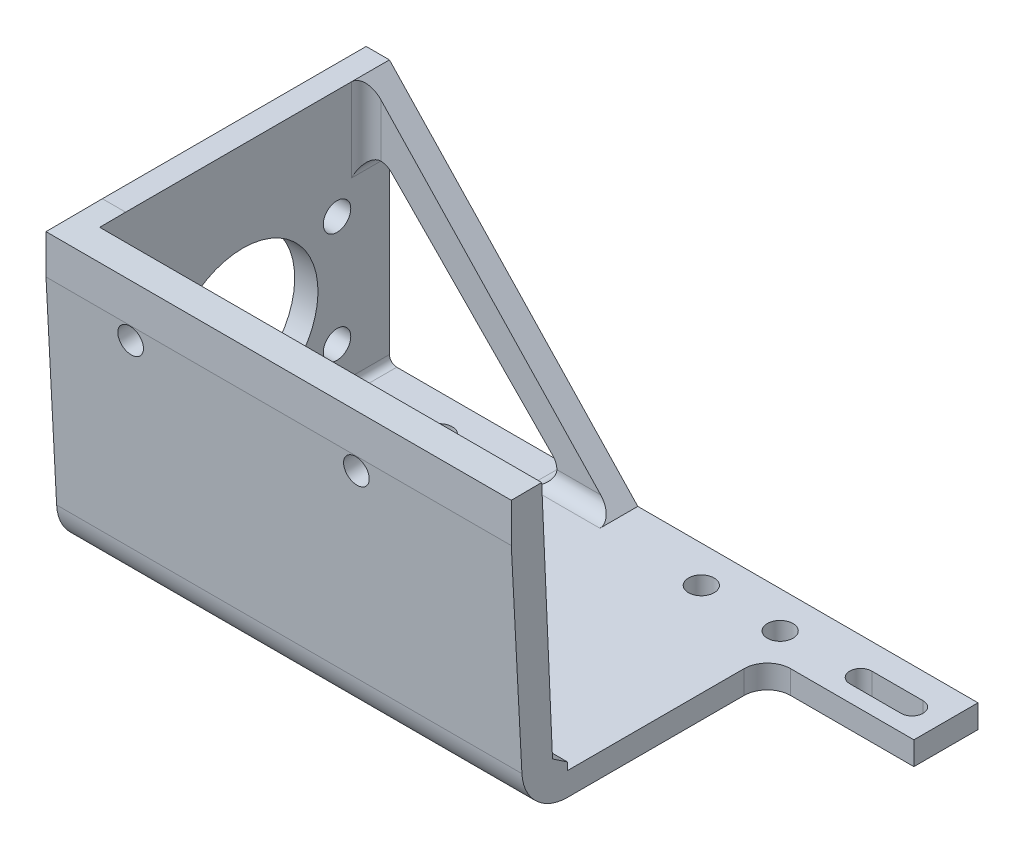
SolidWorks part; units mm, degrees
ref_plane "Front Plane" through (0, 0, 0) normal (0, 0, 1) x (1, 0, 0)
ref_plane "Top Plane" through (0, 0, 0) normal (0, 1, 0) x (1, 0, 0)
ref_plane "Right Plane" through (0, 0, 0) normal (1, 0, 0) x (0, 0, -1)
sketch "Sketch2" plane through (0, 0, 0) normal (0, 0, 1) x (1, 0, 0)
  line L0 (6.35, 78) -> (80, 0.1684)
  line L1 (0, 0) -> (6.35, 0)
  line L2 (0, 0) -> (0, 78)
  line L3 (0, 78) -> (6.35, 78)
  line L4 (6.35, 0) -> (6.35, 65.0327)
  line L6 (6.35, 65.0327) -> (70, 0.1684)
  line L7 (70, 0.1684) -> (80, 0.1684)
  dimension "D1" = 6.35
  dimension "D2" = 78
  dimension "D3" = 80
  dimension "D4" = 10
extrude "Boss-Extrude1" add sketch "Sketch2" along normal blind 80
sketch "Sketch3" plane through (6.35, 0, 0) normal (1, 0, 0) x (0, 0, -1)
  line L0 (0, 0) -> (0, 65.0327) construction
  line L1 (-80, 0) -> (0, 0)
  line L2 (-80, 0) -> (-80, 6.35)
  line L3 (-80, 6.35) -> (0, 6.35)
  line L4 (0, 0) -> (0, 6.35)
  dimension "D1" = 6.35
extrude "Boss-Extrude2" add sketch "Sketch3" along normal blind 160.65
sketch "Sketch8" plane through (0, 6.35, 0) normal (0, 1, 0) x (1, 0, 0)
  line L0 (167, 0) -> (74.1505, 0) construction
  line L1 (6.35, -80) -> (94.6764, -80)
  line L2 (6.35, -80) -> (6.35, -6.35)
  line L3 (6.35, -6.35) -> (94.6764, -6.35)
  line L4 (94.6764, -80) -> (94.6764, -6.35)
  dimension "D1" = 6.35
extrude "Cut-Extrude2" cut sketch "Sketch8" along normal up to next
sketch "Sketch9" plane through (0, 6.35, 0) normal (0, 1, 0) x (1, 0, 0)
  line L1 (167, -80) -> (0, -80)
  line L2 (167, -80) -> (167, -72)
  line L3 (167, -72) -> (0, -72)
  line L4 (0, -80) -> (0, -72)
extrude "Cut-Extrude4" cut sketch "Sketch9" against normal through all both and the other way through all
sketch "Sketch10" plane through (0, 6.35, 0) normal (0, 1, 0) x (1, 0, 0)
  line L0 (167, 0) -> (74.1505, 0) construction
  line L1 (167, -72) -> (127, -72)
  line L2 (167, -72) -> (167, -17.5)
  line L3 (167, -17.5) -> (127, -17.5)
  line L4 (127, -72) -> (127, -17.5)
  dimension "D1" = 17.5
extrude "Cut-Extrude5" cut sketch "Sketch10" against normal up to next
sketch "Sketch11" plane through (0, 6.35, 0) normal (0, 1, 0) x (1, 0, 0)
  line L0 (159, -10) -> (145, -10) construction
  line L1 (159, -13) -> (145, -13)
  line L2 (159, -7) -> (145, -7)
  line L3 (167, 0) -> (167, -17.5) construction
  line L4 (167, 0) -> (74.1505, 0) construction
  line L5 (0, -72) -> (0, 0) construction
  arc A0 (159, -13) -> (159, -7) centre (159, -10) ccw
  arc A1 (145, -7) -> (145, -13) centre (145, -10) ccw
  circle A2 centre (123, -10) radius 3.5
  circle A3 centre (101.48, -10) radius 3.5
  circle A6 centre (101.48, -62) radius 3.5
  circle A9 centre (30, -10) radius 3.5
  point P2 (152, -10)
  point P7 (162, -10)
  dimension "D1" = 14
  dimension "D4" = 30
  dimension "D5" = 22
  dimension "D9" = 65.52
  dimension "D2" = 5
  dimension "D3" = 7
extrude "Cut-Extrude6" cut sketch "Sketch11" against normal up to next
sketch "Sketch12" plane through (6.35, 0, 0) normal (1, 0, 0) x (0, 0, -1)
  line L0 (0, 6.35) -> (0, 65.0327) construction
  line L2 (0, 6.35) -> (-72, 6.35) construction
  circle A0 centre (-66.64, 15.3315) radius 3.75
  circle A1 centre (-66.64, 48.1711) radius 3.75
  circle A2 centre (-14.3, 48.12) radius 3.75
  circle A3 centre (-14.3, 17.9) radius 3.75
  circle A4 centre (-40, 33) radius 20.5
  dimension "D1" = 40
  dimension "D2" = 26.65
  dimension "D3" = 52.34
  dimension "D4" = 30.22
  dimension "D5" = 11.55
  dimension "D6" = 14.3
extrude "Cut-Extrude7" cut sketch "Sketch12" against normal up to next
fillet "Fillet1" radius 4 1 edges at (6.35, 71.5164, 6.35)
fillet "Fillet2" radius 4 1 edges at (6.35, 65.0327, 5.175)
fillet "Fillet3" radius 4 1 edges at (69.0423, 6.35, 6.35)
fillet "Fillet4" radius 4 1 edges at (63.9342, 6.35, 5.175)
fillet "Fillet5" radius 2 1 edges at (6.35, 6.35, 36)
fillet "Fillet6" radius 6.35 1 edges at (127, 3.175, 17.5)
sketch "Sketch17" plane through (0, 0, 0) normal (-1, 0, 0) x (0, 0, 1)
  line L0 (87.3842, 67.2065) -> (84.4829, 11.8458) construction
  line L1 (87.3842, 67.2065) -> (84.4829, 11.8458)
  line L2 (87.3842, 67.2065) -> (87.3842, 77.9122)
  line L3 (87.3842, 77.9122) -> (72, 78)
  line L4 (72, 78) -> (72, 0)
  arc A0 (72, 0) -> (84.4829, 11.8458) centre (72, 12.5) ccw construction
  arc A1 (72, 0) -> (84.4829, 11.8458) centre (72, 12.5) ccw
extrude "Boss-Extrude3" add sketch "Sketch17" against normal up to surface (6.35 mm away) up to face at (6.35, 51.9211, 66.64)
sketch "Sketch18" plane through (6.35, 0, 0) normal (1, 0, 0) x (0, 0, -1)
  line L0 (-87.3842, 77.9122) -> (-87.3842, 67.2065) construction
  line L1 (-87.3842, 67.2065) -> (-84.4829, 11.8458) construction
  line L2 (-87.3842, 77.9122) -> (-87.3842, 67.2065)
  line L3 (-87.3842, 67.2065) -> (-84.4829, 11.8458)
  line L4 (-87.3842, 77.9122) -> (-79.0854, 77.9596)
  line L5 (-72, 78) -> (-87.3842, 77.9122) construction
  line L6 (-79.0854, 77.9596) -> (-76.1342, 11.1534)
  line L7 (-76.1342, 11.1534) -> (-72, 8.35)
  line L8 (-72, 8.35) -> (-72, 0)
  arc A0 (-84.4829, 11.8458) -> (-72, 0) centre (-72, 12.5) ccw construction
  arc A1 (-84.4829, 11.8458) -> (-72, 0) centre (-72, 12.5) ccw
extrude "Boss-Extrude4" add sketch "Sketch18" along normal up to surface (120.65 mm away) up to face at (127, 3.175, 47.925)
sketch "Sketch20" plane through (0, -3.335, 75.4942) normal (0, 0.0441, -0.999) x (-1, 0, 0)
  line L0 (-127, 81.3738) -> (-6.35, 81.3738) construction
  circle A0 centre (-84.5356, 67.3238) radius 3.5
  circle A1 centre (-22.9043, 67.3238) radius 3.5
  dimension "D1" = 14.05
extrude "Cut-Extrude8" cut sketch "Sketch20" against normal up to surface (8.7638 mm away) up to face at (63.5, 39.5262, 85.9335)
